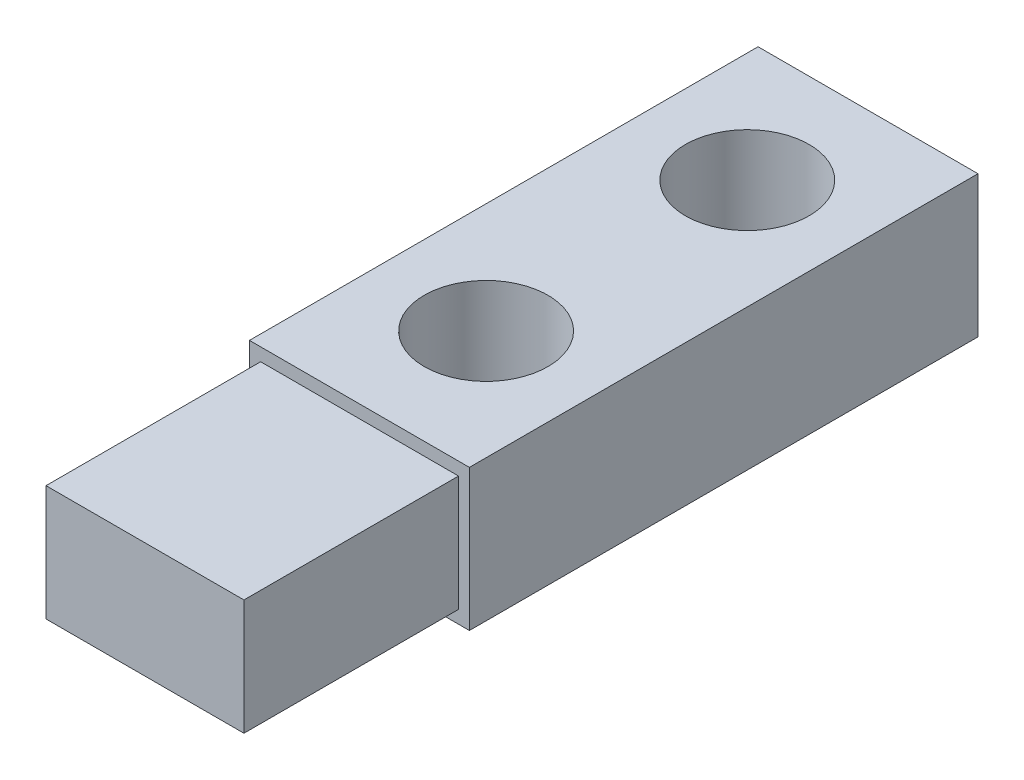
SolidWorks part; units mm, degrees
ref_plane "Front Plane" through (0, 0, 0) normal (0, 0, 1) x (1, 0, 0)
ref_plane "Top Plane" through (0, 0, 0) normal (0, 1, 0) x (1, 0, 0)
ref_plane "Right Plane" through (0, 0, 0) normal (1, 0, 0) x (0, 0, -1)
sketch "Sketch1" plane through (0, 0, 0) normal (0, 1, 0) x (1, 0, 0)
  line L0 (-0.2, -0.7597) -> (-0.2, 3.7403) construction
  line L1 (-0.2, 10.7403) -> (-0.2, 8.7403) construction
  line L2 (-0.2, 1.4903) -> (3.897, 1.4903) construction
  line L3 (3.897, 1.4903) -> (-4.103, 1.4903) construction
  line L4 (-0.2, -7.668) -> (-0.2, -5.7597) construction
  line L5 (-0.2, -0.7597) -> (-0.2, -5.7597) construction
  line L6 (-0.2, -15.668) -> (-0.2, -7.668) construction
  line L7 (-4.206, 10.6387) -> (3.794, 10.6387)
  line L8 (-4.206, 10.6387) -> (-4.206, -7.8613)
  line L9 (-4.206, -7.8613) -> (3.794, -7.8613)
  line L10 (3.794, 10.6387) -> (3.794, -7.8613)
  line L11 (-0.2, -15.668) -> (-0.4, -15.668) construction
  line L12 (-0.4, -15.668) -> (3.4, -15.668) construction
  line L13 (0, -15.668) -> (-3.8, -15.668) construction
  line L15 (3.4, -15.668) -> (-3.8, -15.668)
  line L16 (3.4, -15.668) -> (3.4, -7.8613)
  line L17 (3.4, -7.8613) -> (-3.8, -7.8613)
  line L18 (-3.8, -15.668) -> (-3.8, -7.8613)
  circle A0 centre (-0.2, -3.2597) radius 2.25
  circle A1 centre (-0.2, 6.2403) radius 2.25
  point P24 (0, -15.5837)
  point P25 (-0.7788, -15.4245)
  point P26 (0, -15.668)
  dimension "D1" = 4.5
  dimension "D2" = 18.5
  dimension "D3" = 8
  dimension "D4" = 8
  dimension "D5" = 3.8
  dimension "D6" = 7.2
  dimension "D7" = 7.8067
extrude "Boss-Extrude1" add sketch "Sketch1" along normal blind 5.14 contours L10 L7 L8 L9 A0 A1 region at (-0.2076, 0, -1.3609)
extrude "Boss-Extrude2" add sketch "Sketch1<4>" along normal blind 4.2 from offset 0.47 contours L18 L15 L16 L9 region at (-0.2, 0, 11.7647)
sketch "Sketch1<4>" plane through (0, 0, 0) normal (0, 1, 0) x (1, 0, 0) same geometry as "Sketch1"
